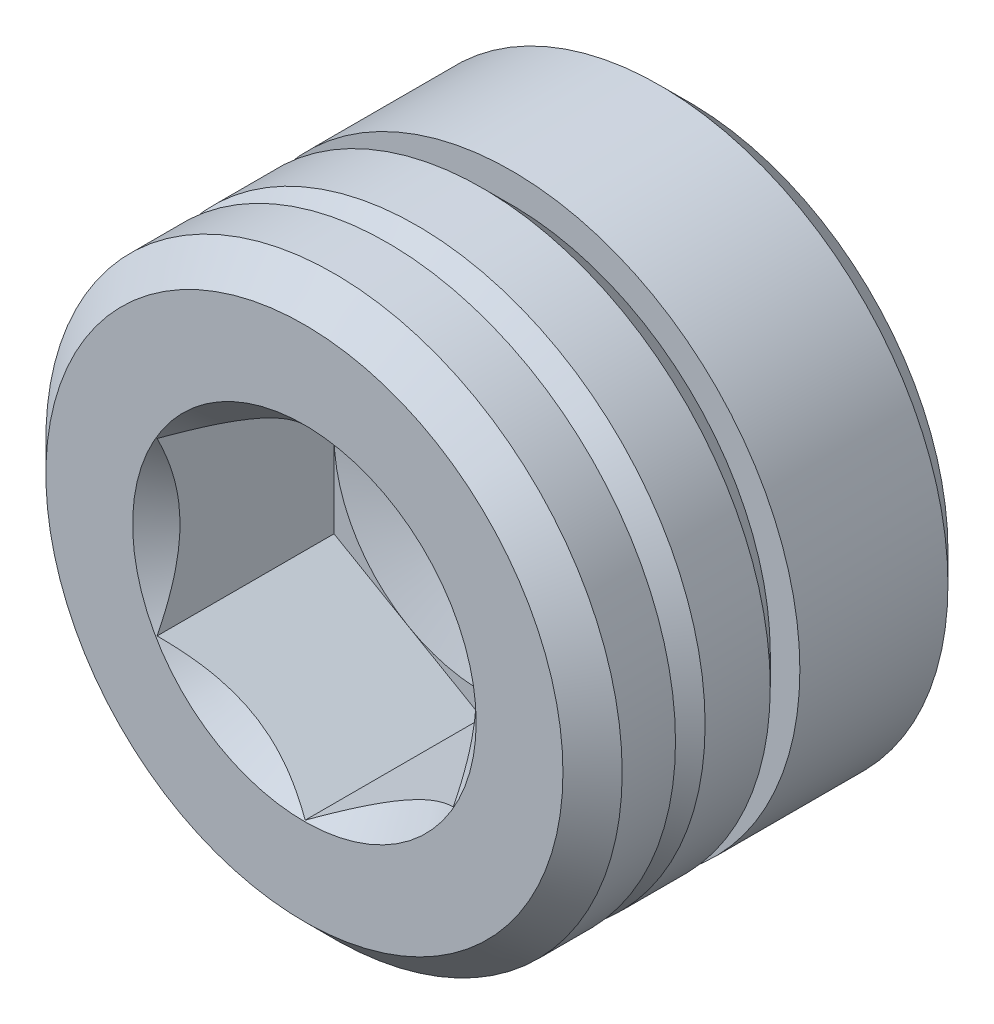
SolidWorks part; units mm, degrees
ref_plane "Front Plane" through (0, 0, 0) normal (0, 0, 1) x (1, 0, 0)
ref_plane "Top Plane" through (0, 0, 0) normal (0, 1, 0) x (1, 0, 0)
ref_plane "Right Plane" through (0, 0, 0) normal (1, 0, 0) x (0, 0, -1)
ref_plane "Plane1" through (0, 0, 0) normal (1, 0, 0) x (0, 0, -1)
sketch "Sketch1" plane through (0, 0, 0) normal (1, 0, 0) x (0, 0, -1)
  line L0 (0, 0) -> (0, 4.365)
  line L1 (0, 4.365) -> (0.5, 4.865)
  line L2 (0.5, 4.865) -> (6, 4.865)
  line L3 (6, 4.865) -> (6.5, 4.365)
  line L4 (6.5, 4.365) -> (6.5, 0)
  line L5 (6.5, 0) -> (0, 0)
  line L6 (6.5, 0) -> (0, 0) construction
revolve "Revolve1" add sketch "Sketch1" angle 360 about L6 reverse direction yes
cosmetic thread "Cosmetic Thread1" parameters "D1"=1.4, "D2"=8.566
cosmetic thread "Cosmetic Thread2" parameters "D1"=3, "D2"=8.566
ref_plane "Plane2" through (0, 0, 0) normal (1, 0, 0) x (0, 0, -1)
sketch "Sketch2" plane through (0, 0, 0) normal (1, 0, 0) x (0, 0, -1)
  line L0 (0, 4.865) -> (1.4, 4.865)
  line L1 (1.4, 4.865) -> (1.4, 4.365)
  line L2 (1.4, 4.365) -> (1.9, 4.865)
  line L3 (1.9, 4.865) -> (3, 4.865)
  line L4 (3, 4.865) -> (3.5, 4.365)
  line L5 (3.5, 4.365) -> (3.5, 4.865)
  line L6 (3.5, 4.865) -> (6.5, 4.865)
  line L7 (6.5, 4.865) -> (6.5, 9.865)
  line L8 (6.5, 9.865) -> (0, 9.865)
  line L9 (0, 9.865) -> (0, 4.865)
  line L10 (6.5, 0) -> (0, 0) construction
revolve "Cut-Revolve1" cut sketch "Sketch2" angle 360 about L10 reverse direction yes
ref_plane "Plane3" through (0, 0, 0) normal (1, 0, 0) x (0, 0, -1)
sketch "Sketch3" plane through (0, 0, 0) normal (1, 0, 0) x (0, 0, -1)
  line L0 (0, 0) -> (0, 2.9)
  line L1 (0, 2.9) -> (0.4, 2.5)
  line L2 (0.4, 2.5) -> (3, 2.5)
  line L3 (3, 2.5) -> (3.6933, 0)
  line L4 (3.6933, 0) -> (0, 0)
  line L5 (3.6933, 0) -> (0, 0) construction
revolve "Cut-Revolve2" cut sketch "Sketch3" angle 360 about L5 reverse direction yes
ref_plane "Plane4" through (0, 0, 0) normal (0, 0, 1) x (1, 0, 0)
sketch "Sketch4" plane through (0, 0, 0) normal (0, 0, 1) x (1, 0, 0)
  line L0 (-2.5, -1.4434) -> (0, -2.8868)
  line L1 (0, -2.8868) -> (2.5, -1.4434)
  line L2 (2.5, -1.4434) -> (2.5, 1.4434)
  line L3 (2.5, 1.4434) -> (0, 2.8868)
  line L4 (0, 2.8868) -> (-2.5, 1.4434)
  line L5 (-2.5, 1.4434) -> (-2.5, -1.4434)
extrude "Cut-Extrude1" cut sketch "Sketch4" against normal blind 3
